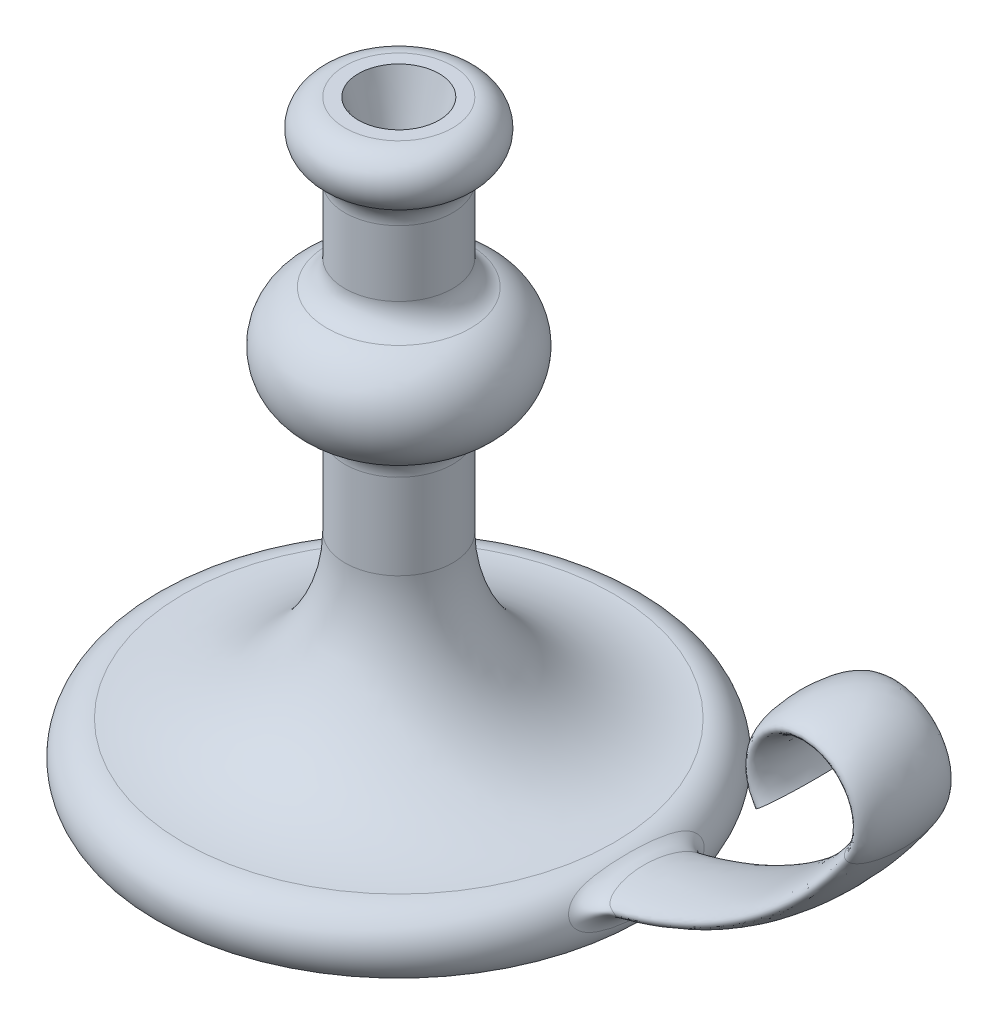
SolidWorks part; units mm, degrees
ref_plane "Front Plane" through (0, 0, 0) normal (0, 0, 1) x (1, 0, 0)
ref_plane "Top Plane" through (0, 0, 0) normal (0, 1, 0) x (1, 0, 0)
ref_plane "Right Plane" through (0, 0, 0) normal (1, 0, 0) x (0, 0, -1)
sketch "Sketch1" plane through (0, 0, 0) normal (0, 0, 1) x (1, 0, 0)
  line L0 (0, 0) -> (90, 0)
  line L1 (0, 220) -> (20, 220)
  line L2 (20, 200) -> (20, 160)
  line L3 (20, 120) -> (20, 80)
  line L4 (0, 220) -> (0, 0) construction
  line L5 (0, 0) -> (0, 220)
  arc A0 (20, 220) -> (20, 200) centre (20, 210) cw
  arc A1 (20, 160) -> (20, 120) centre (20, 140) cw
  arc A2 (20, 80) -> (80, 20) centre (80, 80) ccw
  arc A3 (80, 20) -> (90, 0) centre (80, 7.5) cw
  dimension "D4" = 10
  dimension "D6" = 20
  dimension "D8" = 60
  dimension "D9" = 12.5
  dimension "D1" = 90
  dimension "D2" = 20
  dimension "D3" = 220
  dimension "D5" = 40
  dimension "D7" = 40
revolve "CStick" add sketch "Sketch1" angle 360 about L4
sketch "Sketch2" plane through (0, 0, 0) normal (0, 0, 1) x (1, 0, 0)
  line L0 (0, 10) -> (60, 10)
  line L1 (0, 160) -> (0, 200) construction
  arc A0 (60, 10) -> (183.5921, 75) centre (60, 160) ccw
  arc A1 (183.5921, 75) -> (150.6342, 75) centre (167.1131, 86.3333) ccw
  point P8 (0, 0)
  point P10 (0, 0)
  dimension "D2" = 150
  dimension "D4" = 20
  dimension "D1" = 60
  dimension "D3" = 65
  dimension "D5" = 10
sketch "Sketch3" plane through (0, 0, 0) normal (1, 0, 0) x (0, 0, -1)
  ellipse E0 centre (0, 10) end of major axis (17.5, 10) minor radius 5
  point P1 (0, 0)
  point P7 (0, 0)
  point P8 (0, 0)
  point P9 (0, 0)
  dimension "D1" = 35
  dimension "D2" = 10
sweep "Sweep1" add profiles "Sketch3" path "Sketch2"
sketch "Sketch5" plane through (0, 220, 0) normal (0, 1, 0) x (1, 0, 0)
  circle A0 centre (0, 0) radius 15
  point P3 (0, 0)
  dimension "D1" = 30
extrude "Cut-Extrude1" cut sketch "Sketch5" against normal blind 25 draft 15
fillet "Fillet1" radius 10 4 edges at (89.2995, 13.4828, 17.381) (0, 160, 20) (0, 120, 20) (0, 200, 20)
